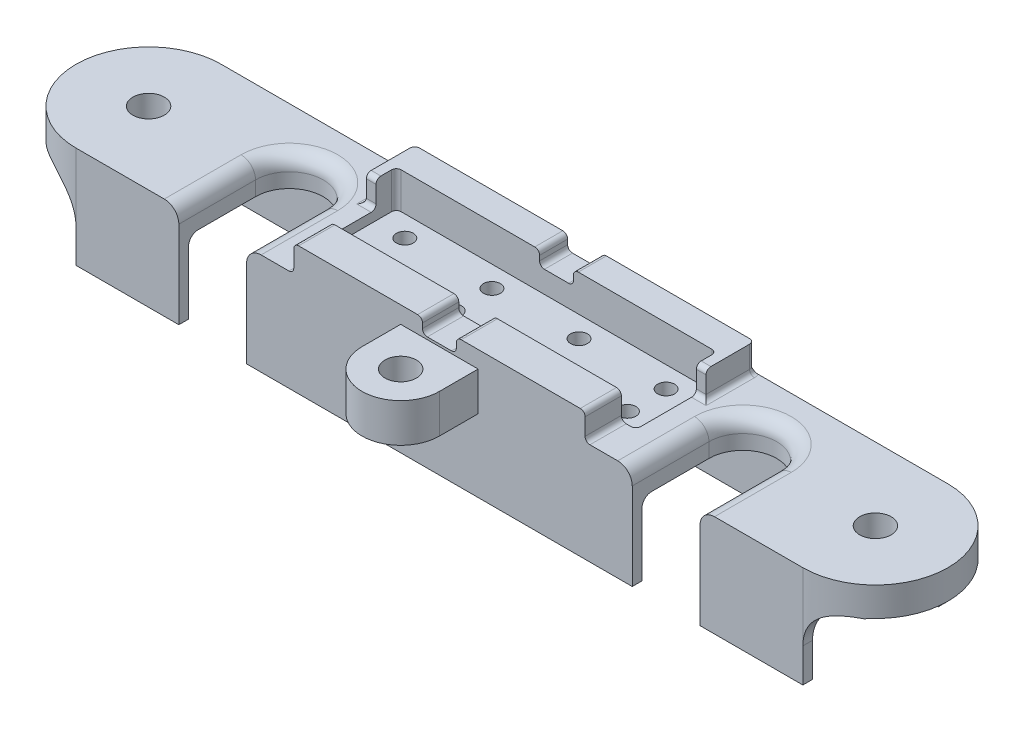
SolidWorks part; units mm, degrees
material "Delrin 2700 NC010, Low Viscosity Acetal Copolymer (SS)"
ref_plane "Front Plane" through (0, 0, 0) normal (0, 0, 1) x (1, 0, 0)
ref_plane "Top Plane" through (0, 0, 0) normal (0, 1, 0) x (1, 0, 0)
ref_plane "Right Plane" through (0, 0, 0) normal (1, 0, 0) x (0, 0, -1)
sketch "Sketch1" plane through (0, 0, 0) normal (0, 1, 0) x (1, 0, 0)
  line L1 (-35.1, -15) -> (0, -15)
  line L2 (-35.1, -15) -> (-35.1, 15)
  line L3 (-35.1, 15) -> (0, 15)
  line L4 (0, -15) -> (0, 15)
  line L5 (-35.1, -15) -> (0, 15) construction
  line L6 (-35.1, 15) -> (0, -15) construction
  point P0 (-17.55, 0)
  point P8 (0, 0)
  dimension "D1" = 35.1
  dimension "D2" = 30
extrude "Boss-Extrude1" add sketch "Sketch1" along normal blind 11.5
shell "Shell1" [suppressed] thickness 1
sketch "Sketch7" plane through (0, 11.5, 0) normal (0, 1, 0) x (1, 0, 0)
  line L0 (0, -15) -> (0, 15) construction
  line L1 (0, -7.5) -> (-33.1, -7.5)
  line L2 (0, -7.5) -> (0, 9.2)
  line L3 (0, 9.2) -> (-33.1, 9.2)
  line L4 (-33.1, -7.5) -> (-33.1, 9.2)
  line L5 (-35.1, -15) -> (0, -15) construction
  line L6 (0, 15) -> (-35.1, 15) construction
  line L7 (-35.1, 15) -> (-35.1, -15) construction
  dimension "D1" = 7.5
  dimension "D2" = 5.8
  dimension "D3" = 2
extrude "Cut-Extrude5" cut sketch "Sketch7" against normal offset from surface (7.5 mm away) 4 up to face at (-17.55, 0, 0)
sketch "Sketch2" plane through (0, 0, 0) normal (0, 1, 0) x (-1, 0, 0)
  line L0 (27, 3.15) -> (9, 3.15) construction
  line L2 (27, 3.15) -> (27, -4.85) construction
  line L3 (27, -4.85) -> (9, -4.85) construction
  line L4 (9, -4.85) -> (9, 3.15) construction
  line L5 (27, -0.85) -> (18.8977, -0.85) construction
  line L6 (17.55, -15) -> (17.55, 15) construction
  line L7 (0, 7.5) -> (0, -9.2) construction
  line L8 (27, -0.85) -> (0, -0.85) construction
  line L9 (0, -15) -> (35.1, -15) construction
  line L10 (35.1, 15) -> (0, 15) construction
  circle A0 centre (27, 3.15) radius 1.75
  circle A1 centre (9, 3.15) radius 1.75
  circle A2 centre (27, -4.85) radius 1.75
  circle A3 centre (9, -4.85) radius 1.75
  circle A5 centre (27, 3.15) radius 2.5 construction
  circle A6 centre (27, -4.85) radius 2.5 construction
  circle A7 centre (9, -4.85) radius 2.5 construction
  circle A8 centre (9, 3.15) radius 2.5 construction
  dimension "D1" = 3.5
  dimension "D4" = 9
  dimension "D5" = 5
  dimension "D2" = 18
  dimension "D3" = 8
extrude "Cut-Extrude1" cut sketch "Sketch2" along normal through all
sketch "Sketch3" [suppressed] plane through (0, 5, 0) normal (0, 1, 0) x (1, 0, 0)
  line L1 (-2.9573, -5.1559) -> (2.9865, -5.139)
  line L2 (2.9865, -5.139) -> (5.9438, 0.0169)
  line L3 (5.9438, 0.0169) -> (2.9573, 5.1559)
  line L4 (2.9573, 5.1559) -> (-2.9865, 5.139)
  line L5 (-2.9865, 5.139) -> (-5.9438, -0.0169)
  line L6 (-5.9438, -0.0169) -> (-2.9573, -5.1559)
  circle A0 centre (0, 0) radius 2.6 construction
  circle A1 centre (0, 0) radius 5.1475 construction
  dimension "D1" = 5.2
extrude "Cut-Extrude2" [suppressed] cut sketch "Sketch3" against normal blind 0.5
sketch "Sketch4" plane through (-35.1, 0, 0) normal (-1, 0, 0) x (0, 0, 1)
  line L0 (-15, 11.5) -> (15, 11.5) construction
  line L1 (-5, 11.5) -> (15, 11.5)
  line L3 (-5, 6) -> (15, 6)
  line L4 (15, 11.5) -> (15, 6)
  line L5 (0, 6) -> (0, 0) construction
  line L11 (-15, 0) -> (15, 0) construction
  line L12 (-5, 6) -> (-5, 11.5)
  dimension "D1" = 5
  dimension "D2" = 5.5
extrude "Cut-Extrude3" cut sketch "Sketch4" against normal offset from surface (5 mm away) 3 up to face at (-33.1, 7.75, -0.85) offset beyond the face yes
sketch "Sketch8" plane through (0, 0, 0) normal (0, -1, 0) x (-1, 0, 0)
  line L0 (35.1, -15) -> (75.1, -15)
  line L1 (35.1, 15) -> (75.1, 15)
  line L2 (35.1, 15) -> (35.1, -15)
  arc A0 (75.1, 15) -> (75.1, -15) centre (75.1, 0) cw
  circle A1 centre (75.1, 0) radius 3.25
  dimension "D2" = 6.5
  dimension "D1" = 40
extrude "bolt extrude" add sketch "Sketch8" against normal blind 6
mirror "Mirror1" about plane through (0, 0, 0) normal (1, 0, 0) of bodies 112 105
fillet "Fillet3" radius 1 8 edges at (30.1, 6, 11.25) (-30.1, 6, 11.25) (30.1, 11.5, 11.25) (-30.1, 11.5, 11.25) (34.1, 11.5, -5) (34.1, 6, -5) (-34.1, 11.5, -5) (-34.1, 6, -5)
fillet "Fillet5" [suppressed] radius 0.5
sketch "Sketch9" plane through (0, 11.5, 0) normal (0, 1, 0) x (1, 0, 0)
  line L0 (35.1, 15) -> (-35.1, 15) construction
  line L1 (-3.5, 15) -> (3.5, 15)
  line L2 (-3.5, 15) -> (-3.5, -15)
  line L3 (-3.5, -15) -> (3.5, -15)
  line L4 (3.5, 15) -> (3.5, -15)
  line L5 (-29.1, -15) -> (29.1, -15) construction
  dimension "D1" = 3.5
  dimension "D2" = 3.5
extrude "Cut-Extrude6" cut sketch "Sketch9" against normal blind 3
fillet "Fillet6" radius 1 14 edges at (35.1, 8.75, -15) (-35.1, 8.75, -15) (-33.1, 5, 7.5) (-33.1, 7.75, -9.2) (33.1, 7.75, -9.2) (33.1, 5, 7.5) (-3.5, 8.5, -12.1) (3.5, 8.5, -12.1) (3.5, 8.5, 11.25) (-3.5, 8.5, 11.25) (3.5, 11.5, 11.25) (-3.5, 11.5, 11.25) (-3.5, 11.5, -12.1) (3.5, 11.5, -12.1)
fillet "Fillet7" [suppressed] radius 1
fillet "Fillet9" radius 1 4 edges at (-35.1, 6, -9) (-34.8071, 6, -14.7071) (35.1, 6, -9) (34.8071, 6, -14.7071)
sketch "Sketch11" plane through (0, 0, 0) normal (0, -1, 0) x (1, 0, 0)
  line L0 (75.1, -15) -> (-75.1, -15) construction
  line L1 (-75.1, 15) -> (75.1, 15) construction
  line L2 (75.1, -15) -> (-75.1, -15)
  line L3 (-75.1, 15) -> (75.1, 15)
  line L4 (-75.1, 13) -> (75.1, 13)
  line L5 (75.1, -13) -> (-75.1, -13)
  line L6 (-75.1, 13) -> (-75.1, 15)
  line L7 (-75.1, -15) -> (-75.1, -13)
  line L8 (75.1, 13) -> (75.1, 15)
  line L9 (75.1, -13) -> (75.1, -15)
  point P9 (75.1, 14)
  dimension "D1" = 2
extrude "Boss-Extrude3" add sketch "Sketch11" along normal blind 15
sketch "Sketch12" plane through (0, 0, 0) normal (0, -1, 0) x (1, 0, 0)
  line L0 (-8, 15) -> (-8, 23)
  line L2 (8, 23) -> (8, 15)
  line L3 (8, 15) -> (-8, 15)
  line L4 (75.1, 15) -> (-75.1, 15) construction
  arc A0 (-8, 23) -> (8, 23) centre (0, 23) cw
  circle A1 centre (0, 23) radius 3.25
  point P2 (0, 0)
  point P6 (0, 15)
  dimension "D1" = 6.5
  dimension "D2" = 8
  dimension "D3" = 8
extrude "Boss-Extrude4" add sketch "Sketch12" against normal blind 8
sketch "Sketch10" plane through (0, 0, 0) normal (0, -1, 0) x (-1, 0, 0)
  line L0 (-39.85, 0.85) -> (-39.85, -15)
  line L1 (75.1, -15) -> (-75.1, -15) construction
  line L2 (-53.85, 0.85) -> (-53.85, -15)
  line L3 (39.85, 0.85) -> (39.85, -15)
  line L4 (53.85, 0.85) -> (53.85, -15)
  line L5 (-53.85, -15) -> (-39.85, -15)
  line L6 (39.85, -15) -> (53.85, -15)
  arc A0 (53.85, 0.85) -> (39.85, 0.85) centre (46.85, 0.85) ccw
  arc A1 (-39.85, 0.85) -> (-53.85, 0.85) centre (-46.85, 0.85) ccw
  dimension "D1" = 14
extrude "Cut-Extrude7" cut sketch "Sketch10" against normal through all and the other way through all
fillet "Fillet10" radius 3 6 edges at (-53.85, 6, 7.075) (-39.85, 6, 7.075) (-46.85, 6, -7.85) (53.85, 6, 7.075) (39.85, 6, 7.075) (46.85, 6, -7.85)
fillet "Fillet11" radius 8 4 edges at (75.1, 0, 14) (-75.1, 0, 14) (-75.1, 0, -14) (75.1, 0, -14)
fillet "Fillet12" radius 2 4 edges at (-68.2167, 0, 13) (68.2167, 0, 13) (0, 0, 13) (0, 0, -13)
